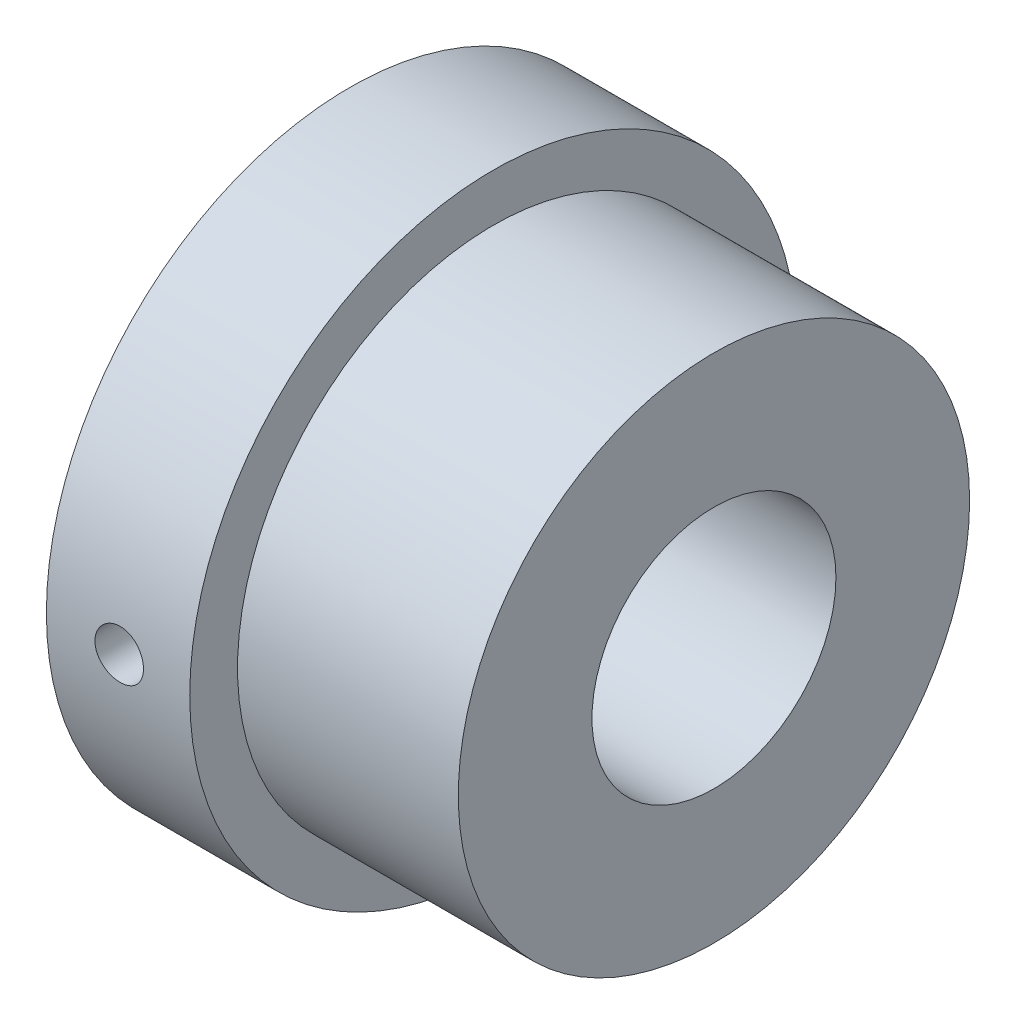
SolidWorks part; units mm, degrees
ref_plane "Front Plane" through (0, 0, 0) normal (0, 0, 1) x (1, 0, 0)
ref_plane "Top Plane" through (0, 0, 0) normal (0, 1, 0) x (1, 0, 0)
ref_plane "Right Plane" through (0, 0, 0) normal (1, 0, 0) x (0, 0, -1)
sketch "Sketch1" plane through (0, 0, 0) normal (1, 0, 0) x (0, 0, -1)
  circle A0 centre (0, 0) radius 6.35
  circle A1 centre (0, 0) radius 2.5527
  dimension "D1" = 5.1054
  dimension "D2" = 12.7
extrude "Boss-Extrude1" add sketch "Sketch1" along normal blind 7.62
sketch "Sketch2" plane through (0, 0, 0) normal (0, 0, 1) x (1, 0, 0)
  line L0 (7.62, 6.35) -> (0, 6.35) construction
  line L1 (3, 6.35) -> (7.62, 6.35)
  line L2 (3, 6.35) -> (3, 5.35)
  line L3 (3, 5.35) -> (7.62, 5.35)
  line L4 (7.62, 6.35) -> (7.62, 5.35)
  line L5 (0, 6.35) -> (0, -6.35) construction
  line L7 (7.62, -6.35) -> (7.62, 6.35) construction
  dimension "D1" = 3
  dimension "D2" = 0
  dimension "D3" = 1
ref_axis "Axis1" through (7.62, 0, 0) along (-1, 0, 0)
revolve "Cut-Revolve1" cut sketch "Sketch2" angle 360 about axis through (7.62, 0, 0) along (-1, 0, 0)
hole_wizard "#60 (0.04) Diameter Hole1" positions "Sketch4" profile "Sketch3" hole size "#60" standard "ANSI Inch"
sketch "Sketch4" plane through (0, 0, 0) normal (0, 0, 1) x (1, 0, 0)
  line L0 (7.62, 0) -> (0, 0) construction
  line L1 (0, 6.35) -> (0, -6.35) construction
  point P0 (1.524, 0)
  dimension "D1" = 1.524
sketch "Sketch3" plane through (1.524, 0, 0) normal (1, 0, 0) x (0, 1, 0)
  line L0 (0, 0) -> (0, 25.7052)
  line L1 (0, 25.7052) -> (0.508, 25.4)
  line L2 (0.508, 25.4) -> (0.508, 0)
  line L5 (0.508, 0) -> (0, 0)
  line L10 (0, 25.7052) -> (-0.508, 25.4) construction
  line L11 (0, -6.35) -> (0, 107.95) construction
  dimension "Hole Dia." = 1.016
  dimension "Hole Depth" = 25.4
  dimension "Drill Angle" = 118
ref_plane "Plane1" through (0, 0, -5.08) normal (0, 0, 1) x (1, 0, 0)
hole_wizard "1/32 (0.03125) Diameter Hole1" positions "Sketch6" profile "Sketch5" hole size "1/32" standard "ANSI Inch" end condition through all
sketch "Sketch6" plane through (0, 0, -5.08) normal (0, 0, 1) x (1, 0, 0)
  line L1 (0, 6.35) -> (0, -6.35) construction
  line L2 (7.62, 0) -> (0, 0) construction
  point P0 (1.524, -5.08)
  dimension "D1" = 1.524
  dimension "D2" = 5.08
sketch "Sketch5" plane through (1.524, -5.08, -5.08) normal (1, 0, 0) x (0, 1, 0)
  line L0 (0, 0) -> (0, 11.43)
  line L1 (0, 11.43) -> (0.3969, 11.43)
  line L2 (0.3969, 11.43) -> (0.3969, 0)
  line L5 (0.3969, 0) -> (0, 0)
  line L11 (0, -6.35) -> (0, 107.95) construction
  dimension "Thru Hole Dia." = 0.7937
  dimension "Thru Hole Depth" = 11.43
